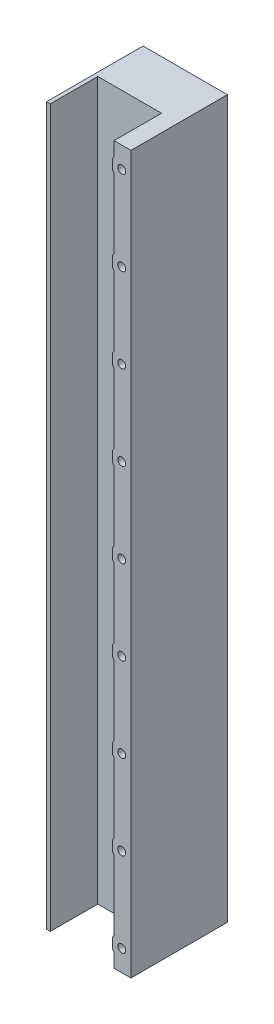
SolidWorks part; units mm, degrees
ref_plane "Top" through (0, 0, 0) normal (0, 0, 1) x (1, 0, 0)
ref_plane "Front" through (0, 0, 0) normal (0, 1, 0) x (1, 0, 0)
ref_plane "Right" through (0, 0, 0) normal (1, 0, 0) x (0, 0, -1)
sketch "Profile Sketch" plane through (0.0456, 0, -0.0242) normal (0, 1, 0) x (-1, 0, 0)
  line L1 (16.0456, 0.0242) -> (0.0456, 0.0242)
  line L2 (0.0456, 0.0242) -> (0.0456, -18.2758)
  line L3 (0.0456, -18.2758) -> (16.0456, -18.2758)
  line L5 (16.0456, -18.2758) -> (16.0456, 0.0242)
  line L12 (16.0456, 0.3949) -> (16.0456, 1.3939) construction
  line L13 (1.7956, 0.0242) -> (1.7956, 4.0449) construction
  dimension "D2" = 1.75
  dimension "Reel Width" = 16
  dimension "Height" = 18.3
extrude "Profile Extrude" add sketch "Profile Sketch" along normal blind 136
sketch "Pocket Sketch" plane through (0, 0, 0) normal (0, 1, 0) x (1, 0, 0)
  line L0 (-1.75, 0) -> (-1.75, -2.6213) construction
  line L2 (-16, 0) -> (0, 0) construction
  line L4 (-15.3, 0) -> (-3.2, 0)
  line L5 (-15.3, 0) -> (-15.3, 9)
  line L6 (-15.3, 9) -> (-3.2, 9)
  line L7 (-3.2, 0) -> (-3.2, 9)
  point P9 (-9.25, 0)
  dimension "D1" = 1.75
  dimension "Width" = 12.1
  dimension "Depth" = 9
  dimension "Center From Pins" = 7.5
extrude "Pocket Cut" cut sketch "Pocket Sketch" along normal through all
sketch "Index Hole Sketch" plane through (0, 0, 0) normal (0, 0, 1) x (1, 0, 0)
  circle A0 centre (-1.75, 4) radius 0.75
  dimension "D2" = 1.5
  dimension "D3" = 4
  dimension "D1" = 1.75
extrude "First Index Hole Cut" cut sketch "Index Hole Sketch" against normal blind 8
sketch "Index Hole Reinforcement Sketch" plane through (0, 0, 0) normal (0, 0, 1) x (1, 0, 0)
  line L0 (-3.5, 4.9682) -> (-3.5, 3.0318)
  line L1 (-3.2, 5.3775) -> (-3.2, 2.6225)
  line L2 (-3.2, 136) -> (-3.2, 0) construction
  arc A0 (-3.2, 5.3775) -> (-3.5, 4.9682) centre (-1.75, 4) ccw
  arc A1 (-3.5, 3.0318) -> (-3.2, 2.6225) centre (-1.75, 4) ccw
  dimension "D1" = 2
  dimension "D2" = 1.75
extrude "Index Hole Reinforcement" add sketch "Index Hole Reinforcement Sketch" against normal up to next
pattern_linear "Index Hole Pattern" count 9 spacing 16 along (0, 1, 0) of "First Index Hole Cut", "Index Hole Reinforcement"
ref_plane "Mid Plane" through (0, 68, 0) normal (0, -1, 0) x (-1, 0, 0)
equation "\"D2@Index Hole Sketch\"=1.50mm"
